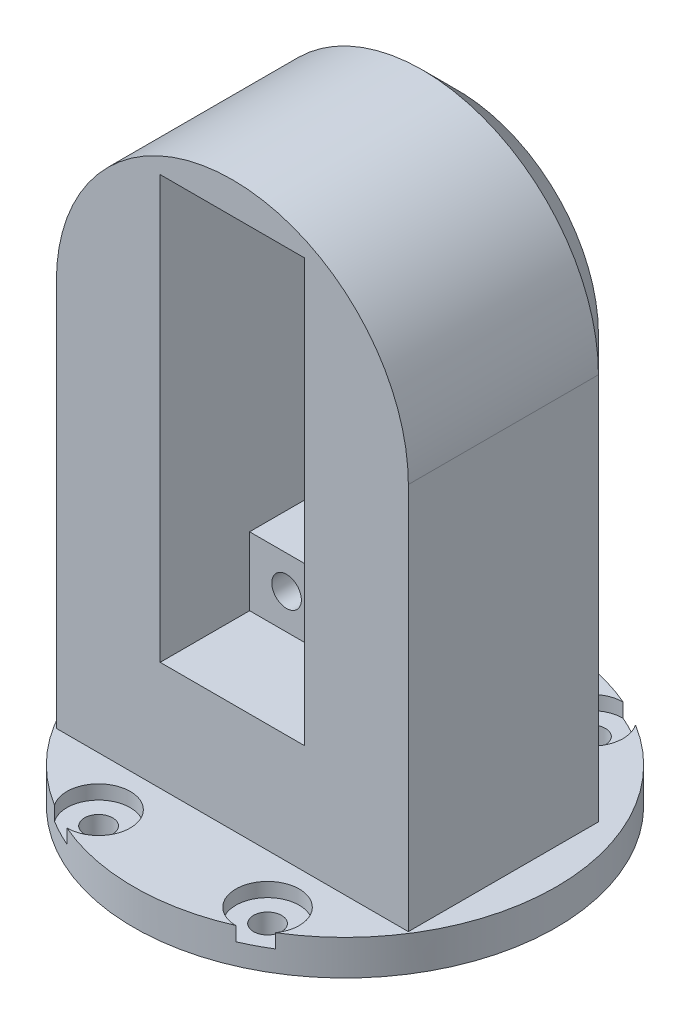
SolidWorks part; units mm, degrees
ref_plane "Front Plane" through (0, 0, 0) normal (0, 0, 1) x (1, 0, 0)
ref_plane "Top Plane" through (0, 0, 0) normal (0, 1, 0) x (1, 0, 0)
ref_plane "Right Plane" through (0, 0, 0) normal (1, 0, 0) x (0, 0, -1)
sketch "Sketch1" plane through (0, 0, 0) normal (0, 0, 1) x (1, 0, 0)
  line L0 (0, 0) -> (0, 147.804) construction
  line L1 (25, 51) -> (-25, 51)
  line L2 (43.2, 51) -> (-43.2, 51) construction
  line L3 (-25, 51) -> (-25, 111)
  line L5 (25, 51) -> (25, 111)
  arc A0 (25, 111) -> (-25, 111) centre (0, 111) ccw
  point P11 (0, 51)
  dimension "D1" = 25
  dimension "D2" = 60
extrude "Boss-Extrude1" add sketch "Sketch1" along normal mid plane 32
chamfer "Chamfer1" distance 5 angle 45 3 edges at (25, 81, -16) (-25, 81, -16) (0, 136, -16)
sketch "Sketch3" plane through (0, 0, 0) normal (1, 0, 0) x (0, 0, -1)
  line L0 (-3.3, 101.5) -> (33.5262, 101.5) construction
  line L1 (-3.3, 77.5) -> (-3.3, 125.5) construction
  line L2 (-3.3, 121.79) -> (-3.3, 131.5)
  line L3 (-3.3, 131.5) -> (-16, 131.5)
  line L4 (-16, 136) -> (-16, 111) construction
  line L5 (-3.3, 121.79) -> (16, 121.79)
  line L6 (16, 111) -> (16, 131) construction
  line L7 (16, 121.79) -> (16, 101.5)
  line L8 (16, 111) -> (16, 51) construction
  line L9 (16, 101.5) -> (-16, 101.5)
  line L10 (-16, 51) -> (-16, 111) construction
  line L11 (-16, 101.5) -> (-16, 131.5)
  line L12 (-6.3, 128.5) -> (-3.3, 128.5) construction
  line L13 (-3.3, 121.49) -> (16.7, 121.49) construction
  dimension "D1" = 3
  dimension "D2" = 0.3
extrude "Cut-Extrude1" cut sketch "Sketch3" against normal mid plane 20.5
ref_axis "Axis1" through (-6, 126.5, 1.7046) along (0, 0, 1)
sketch "Sketch9" plane through (0, 0, 3.3) normal (0, 0, 1) x (1, 0, 0)
  line L0 (8.25, 126.5) -> (-8.25, 126.5) construction
  arc A0 (4.4736, 128.1531) -> (7.6279, 128.0532) centre (6, 126.5) ccw construction
  arc A1 (-7.6279, 128.0532) -> (-4.4736, 128.1531) centre (-6, 126.5) ccw construction
  circle A2 centre (-5, 126.5) radius 2
  dimension "D1" = 4
  dimension "D2" = 1
ref_plane "Plane1" through (-5, 0, 0) normal (1, 0, 0) x (0, 0, -1)
sketch "Sketch4" plane through (-5, 0, 0) normal (1, 0, 0) x (0, 0, -1)
  line L0 (-1.7046, 126.5) -> (-6.2046, 126.5) construction
  line L1 (-3.3, 126.5) -> (6.7, 126.5)
  line L2 (-3.3, 121.79) -> (-3.3, 131.5) construction
  line L3 (-3.3, 126.5) -> (-3.3, 128.6)
  line L4 (-3.3, 128.6) -> (2.7, 128.6)
  line L5 (2.7, 128.6) -> (2.7, 127.85)
  line L6 (2.7, 127.85) -> (6.7, 127.85)
  line L7 (6.7, 127.85) -> (6.7, 126.5)
  dimension "D1" = 10
  dimension "D2" = 2.1
  dimension "D3" = 1.35
  dimension "D4" = 6
revolve "Cut-Revolve1" cut sketch "Sketch4" angle 360 about L1
ref_plane "Plane2" through (0, 0, 0) normal (1, 0, 0) x (0, 0, -1)
mirror "Mirror1" about plane through (0, 0, 0) normal (1, 0, 0) of "Cut-Revolve1"
mirror "Mirror2" about plane through (-10.25, 101.5, -16) normal (0, -1, 0) of "Mirror1", "Cut-Extrude1"
sketch "Sketch5" plane through (0, 0, 3.3) normal (0, 0, 1) x (1, 0, 0)
  line L0 (-10.25, 121.79) -> (10.25, 121.79) construction
  line L1 (-3.2, 121.79) -> (3.2, 121.79)
  line L2 (-3.2, 121.79) -> (-3.2, 128.5)
  line L3 (-3.2, 128.5) -> (3.2, 128.5)
  line L4 (3.2, 121.79) -> (3.2, 128.5)
  line L6 (4.3379, 128.5) -> (-4.3379, 128.5) construction
  line L7 (3.2, 127.5) -> (3.2, 122.5) construction
  line L8 (-3.2, 127.5) -> (-3.2, 122.5) construction
extrude "Cut-Extrude2" cut sketch "Sketch5" against normal blind 24
sketch "Sketch6" plane through (0, 0, -16) normal (0, 0, -1) x (-1, 0, 0)
  line L6 (-15, 111) -> (-15, 56)
  line L7 (-15, 56) -> (15, 56)
  line L8 (15, 56) -> (15, 111)
  line L9 (-15, 111) -> (-15, 56)
  line L10 (-15, 56) -> (15, 56)
  line L11 (15, 56) -> (15, 111)
  arc A2 (15, 111) -> (-15, 111) centre (0, 111) ccw
  arc A3 (15, 111) -> (-15, 111) centre (0, 111) ccw
  dimension "D1" = 5
extrude "Cut-Extrude3" cut sketch "Sketch6" against normal blind 10
fillet "Fillet1" radius 15 2 edges at (-15, 56, -11) (15, 56, -11)
chamfer "Chamfer2" distance 3 angle 45 5 edges at (-15, 91, -16) (-10.6066, 60.3934, -16) (11.6833, 120.4074, -16) (10.6066, 60.3934, -16) (15, 91, -16)
sketch "Sketch7" plane through (0, 51, 0) normal (0, -1, 0) x (1, 0, 0)
  circle A0 centre (0, 0) radius 30 construction
  circle A1 centre (0, 0) radius 30
  circle A2 centre (-12, -23) radius 2 construction
  circle A3 centre (-12, -23) radius 2
  circle A4 centre (12, -23) radius 2 construction
  circle A5 centre (12, -23) radius 2
  circle A6 centre (-12, 23) radius 2 construction
  circle A7 centre (-12, 23) radius 2
  circle A8 centre (12, 23) radius 2 construction
  circle A9 centre (12, 23) radius 2
extrude "Boss-Extrude2" add sketch "Sketch7" against normal blind 5
sketch "Sketch8" plane through (0, 56, 0) normal (0, 1, 0) x (1, 0, 0)
  circle A0 centre (12, 23) radius 4.5
  circle A1 centre (-12, 23) radius 4.5
  circle A2 centre (-12, -23) radius 4.5
  circle A3 centre (12, -23) radius 4.5
  dimension "D1" = 9
extrude "Cut-Extrude4" cut sketch "Sketch8" against normal blind 2
